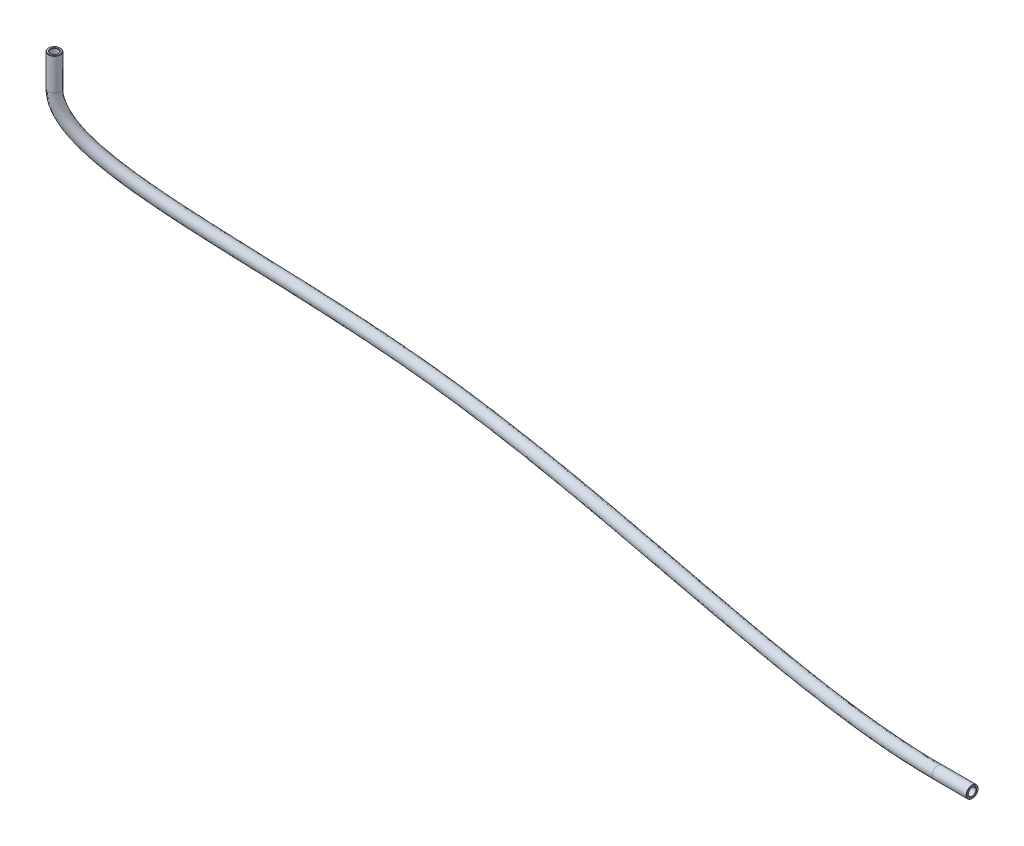
SolidWorks part; units mm, degrees
ref_plane "Front Plane" through (0, 0, 0) normal (0, 0, 1) x (1, 0, 0)
ref_plane "Top Plane" through (0, 0, 0) normal (0, 1, 0) x (1, 0, 0)
ref_plane "Right Plane" through (0, 0, 0) normal (1, 0, 0) x (0, 0, -1)
sketch3d "3DSketch1"
  line L0 (-47.1911, -46.6, -27.0013) -> (-47.1911, -35.8, -27.0013)
  line L1 (237.525, -110.4823, -40.125) -> (249.105, -110.4823, -40.125)
  spline S0 degree 3 poles (237.525, -110.4823, -40.125) (187.824, -110.4823, -40.125) (43.0615, -99.4551, -73.9028) (-47.1911, -67.0132, -27.0013) (-47.1911, -46.6, -27.0013) knots 0 0 0 0 0.523134 1 1 1 1
sketch "Sketch1" plane through (239.725, 0, 0) normal (-1, 0, 0) x (0, 0, 1)
  circle A0 centre (-40.125, -110.4823) radius 2
  circle A1 centre (-40.125, -110.4823) radius 1.3
  circle A2 centre (-40.125, -110.4823) radius 3.5386 construction
  dimension "D1" = 2.6
  dimension "D2" = 4
sweep "Sweep1" add profiles "Sketch1" path "3DSketch1"
chamfer "Chamfer1" distance 0.127 angle 45 4 edges at (249.105, -112.4823, -40.125) (249.105, -111.7823, -40.125) (-48.6431, -35.8, -25.6258) (-48.1349, -35.8, -26.1072)
